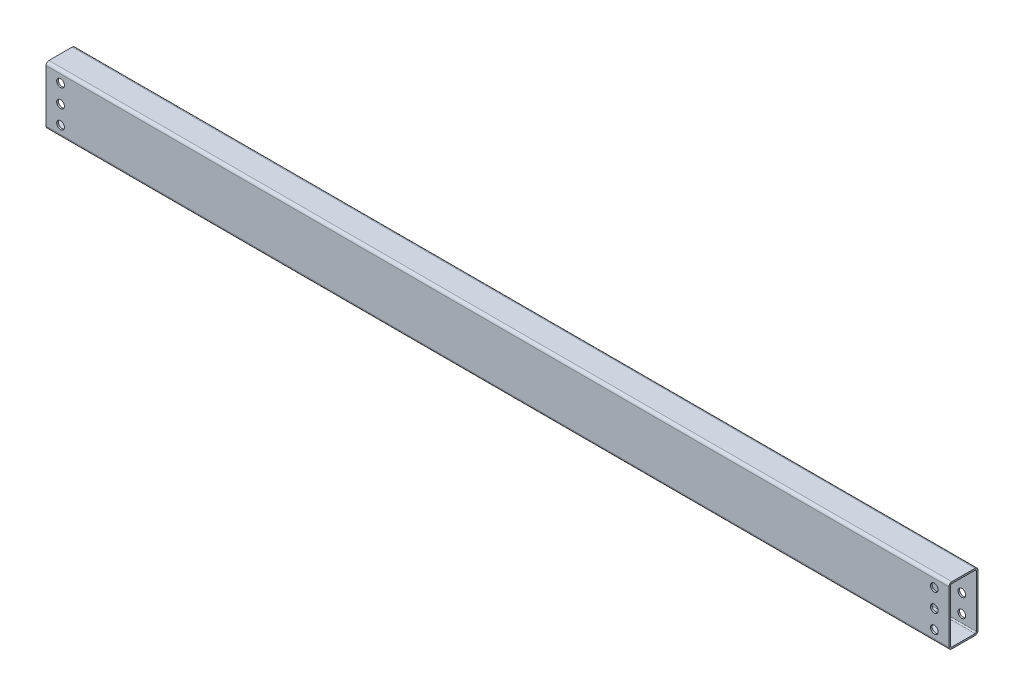
SolidWorks part; units mm, degrees
material "6061-T6 (SS)"
ref_plane "Front" through (0, 0, 0) normal (0, 0, 1) x (1, 0, 0)
ref_plane "Top" through (0, 0, 0) normal (0, 1, 0) x (1, 0, 0)
ref_plane "Right" through (0, 0, 0) normal (1, 0, 0) x (0, 0, -1)
sketch "Sketch1" plane through (0, 0, 0) normal (1, 0, 0) x (0, 0, -1)
  line L0 (10.16, -25.4) -> (-10.16, -25.4)
  line L1 (12.7, -22.86) -> (12.7, 22.86)
  line L2 (10.16, 25.4) -> (-10.16, 25.4)
  line L3 (-12.7, -22.86) -> (-12.7, 22.86)
  line L4 (12.7, -25.4) -> (-12.7, 25.4) construction
  line L5 (12.7, 25.4) -> (-12.7, -25.4) construction
  arc A0 (-10.16, -25.4) -> (-12.7, -22.86) centre (-10.16, -22.86) cw
  arc A1 (10.16, -25.4) -> (12.7, -22.86) centre (10.16, -22.86) ccw
  arc A2 (12.7, 22.86) -> (10.16, 25.4) centre (10.16, 22.86) ccw
  arc A3 (-10.16, 25.4) -> (-12.7, 22.86) centre (-10.16, 22.86) ccw
  point P0 (0, 0)
  dimension "D3" = 2.54
  dimension "D1" = 25.4
  dimension "D2" = 50.8
extrude "Extrude-Thin1" add sketch "Sketch1" along normal mid plane 787.4 thin thin type one direction reverse wall 1.4478
hole_wizard "1/4 Clearance Hole1" positions "Sketch2" profile "Sketch3" hole size "1/4" standard "ANSI Inch" end condition through all
sketch "Sketch2" plane through (0, 0, -12.7) normal (0, 0, -1) x (-1, 0, 0)
  line L0 (-393.7, -22.86) -> (-393.7, 22.86) construction
  line L1 (-393.7, 25.4) -> (393.7, 25.4) construction
  line L2 (-393.7, -25.4) -> (393.7, -25.4) construction
  line L3 (-381, 15.875) -> (-381, -15.875) construction
  line L4 (0, 0) -> (0, -37.3791) construction
  point P0 (-381, 15.875)
  point P2 (-381, -15.875)
  point P15 (-381, 0)
  point P23 (381, -15.875)
  point P24 (381, 0)
  point P25 (381, 15.875)
  dimension "D1" = 12.7
  dimension "D2" = 9.525
  dimension "D3" = 9.525
sketch "Sketch3" plane through (381, 15.875, -12.7) normal (1, 0, 0) x (0, 1, 0)
  line L0 (0, 0) -> (0, 25.4)
  line L1 (0, 25.4) -> (3.3782, 25.4)
  line L2 (3.3782, 25.4) -> (3.3782, 0)
  line L5 (3.3782, 0) -> (0, 0)
  line L11 (0, -6.35) -> (0, 107.95) construction
  dimension "Thru Hole Dia." = 6.7564
  dimension "Thru Hole Depth" = 25.4
hole_wizard "1/4 Clearance Hole2" positions "Sketch4" profile "Sketch5" hole size "1/4" standard "ANSI Inch" end condition up to next
sketch "Sketch4" plane through (0, 0, -12.7) normal (0, 0, -1) x (-1, 0, 0)
  line L0 (-234.95, 15.875) -> (-234.95, -15.875) construction
  line L2 (-393.7, 25.4) -> (393.7, 25.4) construction
  line L3 (-393.7, -25.4) -> (393.7, -25.4) construction
  line L4 (0, 0) -> (0, -51.4899) construction
  point P19 (-234.95, 15.875)
  point P21 (-234.95, 0)
  point P23 (-234.95, -15.875)
  point P42 (234.95, -15.875)
  point P43 (234.95, 0)
  point P44 (234.95, 15.875)
  dimension "D1" = 9.525
  dimension "D2" = 9.525
  dimension "D3" = 469.9
sketch "Sketch5" plane through (234.95, 15.875, -12.7) normal (1, 0, 0) x (0, 1, 0)
  line L0 (0, 0) -> (0, 1.4478)
  line L1 (0, 1.4478) -> (3.3782, 1.4478)
  line L2 (3.3782, 1.4478) -> (3.3782, 0)
  line L5 (3.3782, 0) -> (0, 0)
  line L11 (0, -6.35) -> (0, 107.95) construction
  dimension "Thru Hole Dia." = 6.7564
  dimension "Thru Hole Depth" = 1.4478
sketch "Sketch6" plane through (0, 0, -12.7) normal (0, 0, -1) x (-1, 0, 0)
  line L0 (-393.7, -25.4) -> (393.7, -25.4) construction
  line L2 (-120.65, -25.4) -> (-107.95, -25.4)
  line L3 (-120.65, -25.4) -> (-120.65, -9.525)
  line L4 (-117.475, -6.35) -> (-111.125, -6.35)
  line L5 (-107.95, -25.4) -> (-107.95, -9.525)
  line L6 (-44.45, -25.4) -> (-31.75, -25.4)
  line L11 (-44.45, -25.4) -> (-44.45, -9.525)
  line L12 (-41.275, -6.35) -> (-34.925, -6.35)
  line L13 (-31.75, -25.4) -> (-31.75, -9.525)
  line L14 (31.75, -25.4) -> (44.45, -25.4)
  line L15 (31.75, -25.4) -> (31.75, -9.525)
  line L16 (34.925, -6.35) -> (41.275, -6.35)
  line L17 (44.45, -25.4) -> (44.45, -9.525)
  line L18 (107.95, -25.4) -> (120.65, -25.4)
  line L19 (107.95, -25.4) -> (107.95, -9.525)
  line L20 (111.125, -6.35) -> (117.475, -6.35)
  line L21 (120.65, -25.4) -> (120.65, -9.525)
  line L22 (0, 0) -> (0, -9.525) construction
  arc A0 (-111.125, -6.35) -> (-107.95, -9.525) centre (-111.125, -9.525) cw
  arc A1 (-120.65, -9.525) -> (-117.475, -6.35) centre (-117.475, -9.525) cw
  arc A4 (-34.925, -6.35) -> (-31.75, -9.525) centre (-34.925, -9.525) cw
  arc A5 (-44.45, -9.525) -> (-41.275, -6.35) centre (-41.275, -9.525) cw
  arc A6 (41.275, -6.35) -> (44.45, -9.525) centre (41.275, -9.525) cw
  arc A7 (31.75, -9.525) -> (34.925, -6.35) centre (34.925, -9.525) cw
  arc A8 (117.475, -6.35) -> (120.65, -9.525) centre (117.475, -9.525) cw
  arc A9 (107.95, -9.525) -> (111.125, -6.35) centre (111.125, -9.525) cw
  dimension "D1" = 3.175
  dimension "D2" = 12.7
  dimension "D3" = 19.05
  dimension "D5" = 76.2
  dimension "D4" = 4
extrude "Cut-Extrude1" cut sketch "Sketch6" against normal blind 9.525
